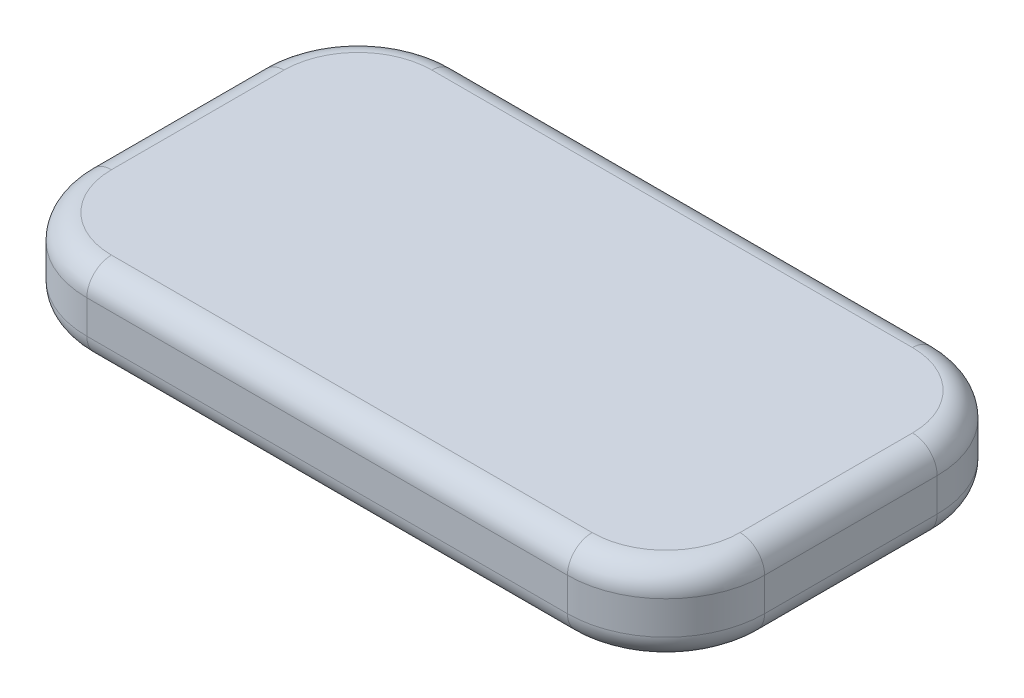
SolidWorks part; units mm, degrees
ref_plane "Front Plane" through (0, 0, 0) normal (0, 0, 1) x (1, 0, 0)
ref_plane "Top Plane" through (0, 0, 0) normal (0, 1, 0) x (1, 0, 0)
ref_plane "Right Plane" through (0, 0, 0) normal (1, 0, 0) x (0, 0, -1)
sketch "Sketch2" plane through (0, 0, 0) normal (0, 1, 0) x (1, 0, 0)
  line L1 (0, 0) -> (139.7, 0)
  line L2 (0, 0) -> (0, 76.2)
  line L3 (0, 76.2) -> (139.7, 76.2)
  line L4 (139.7, 0) -> (139.7, 76.2)
  dimension "D1" = 139.7
  dimension "D2" = 76.2
extrude "Boss-Extrude1" add sketch "Sketch2" along normal blind 17.018 contours L2 L1 L4 L3
fillet "Fillet1" radius 20.32 4 edges at (139.7, 8.509, 0) (139.7, 8.509, -76.2) (0, 8.509, -76.2) (0, 8.509, 0)
fillet "Fillet2" radius 5.08 8 edges at (5.9516, 17.018, -5.9516) (69.85, 17.018, 0) (133.7484, 17.018, -5.9516) (139.7, 17.018, -38.1) (133.7484, 17.018, -70.2484) (69.85, 17.018, -76.2) (5.9516, 17.018, -70.2484) (0, 17.018, -38.1)
fillet "Fillet3" radius 5.08 8 edges at (5.9516, 0, -5.9516) (69.85, 0, 0) (133.7484, 0, -5.9516) (139.7, 0, -38.1) (133.7484, 0, -70.2484) (69.85, 0, -76.2) (5.9516, 0, -70.2484) (0, 0, -38.1)
